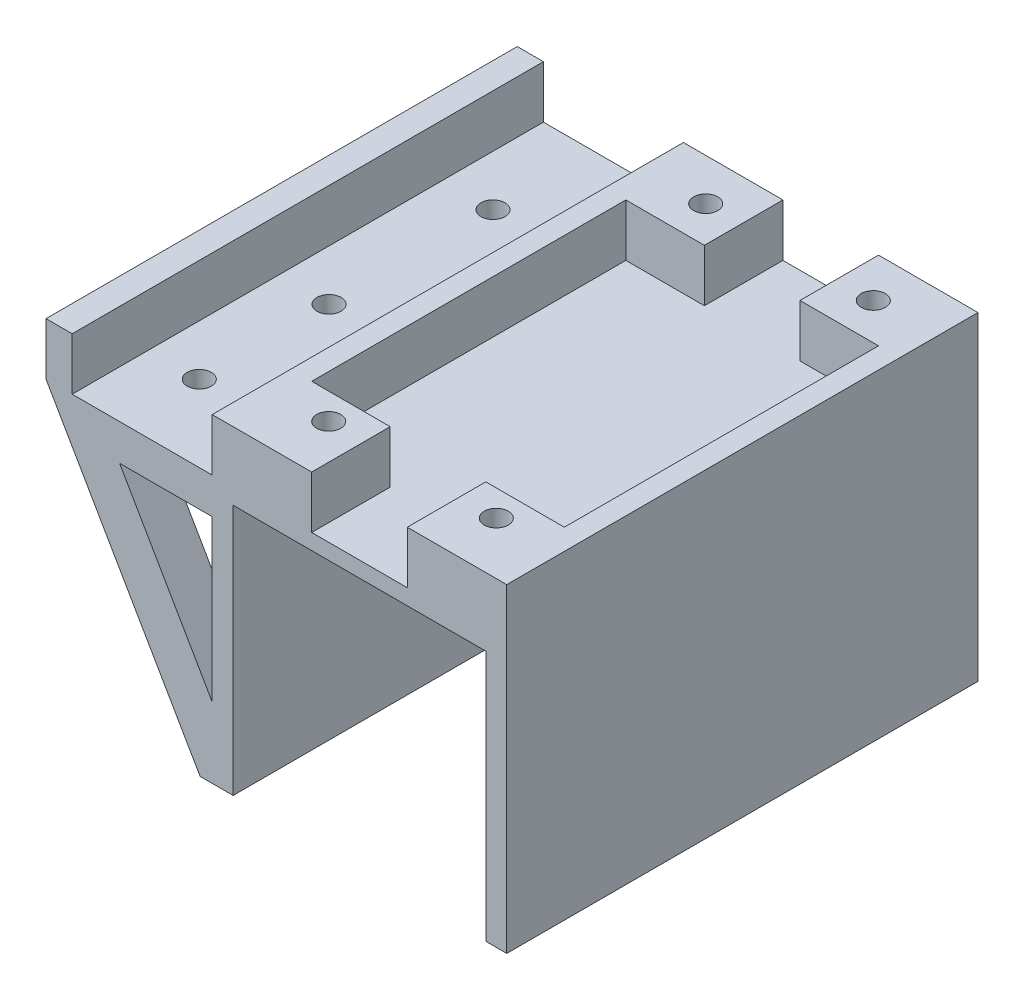
SolidWorks part; units mm, degrees
ref_plane "Front" through (0, 0, 0) normal (0, 0, 1) x (1, 0, 0)
ref_plane "Top" through (0, 0, 0) normal (0, 1, 0) x (1, 0, 0)
ref_plane "Right" through (0, 0, 0) normal (1, 0, 0) x (0, 0, -1)
sketch "Sketch1" plane through (0, 0, 0) normal (0, 0, 1) x (1, 0, 0)
  line L0 (0, 0) -> (0, 70)
  line L1 (0, 70) -> (56.254, 70)
  line L2 (56.254, 70) -> (56.254, 0)
  line L3 (56.254, 0) -> (52.254, 0)
  line L4 (52.254, 0) -> (52.254, 65)
  line L5 (52.254, 65) -> (4, 65)
  line L6 (4, 65) -> (4, 0)
  line L7 (4, 0) -> (0, 0)
  line L9 (4, 55) -> (52.254, 55)
  line L10 (4, 55) -> (4, 52)
  line L11 (4, 52) -> (52.254, 52)
  line L12 (52.254, 55) -> (52.254, 52)
  dimension "D1" = 48.254
  dimension "D2" = 4
  dimension "D3" = 4
  dimension "D4" = 5
  dimension "D5" = 70
  dimension "D6" = 3
  dimension "D7" = 10
extrude "Boss-Extrude1" add sketch "Sketch1" along normal blind 70 contours L7 L6 L5 L4 L3 L2 L1 L0 | L9 L12 L11 L10 region at (0.898, 35, 0)
sketch "Sketch3" plane through (0, 0, 70) normal (0, 0, 1) x (1, 0, 0)
  line L0 (0, 70) -> (-40.3946, 70)
  line L1 (-40.3946, 70) -> (0, 0.0344)
  line L2 (0, 0) -> (0, 70) construction
  line L3 (0, 0.0344) -> (0, 70)
  line L4 (0, 70) -> (0, 62.5)
  line L5 (0, 62.5) -> (-26, 62.5)
  line L6 (-26, 62.5) -> (0, 17.4667)
  line L7 (0, 17.4667) -> (0, 0.0344)
  line M11 (0, 70) -> (0, 0)
  dimension "D1" = 60
  dimension "D2" = 180
  dimension "D3" = 7.5
  dimension "D4" = 26
extrude "Boss-Extrude3" add sketch "Sketch3" against normal blind 8 contours L6 L5 L0 L1 M11 region at (-16.8587, 46.1047, 70)
sketch "Sketch4" plane through (0, 0, 0) normal (0, 0, -1) x (-1, 0, 0)
  line L0 (0, 70) -> (40.3946, 70)
  line L1 (40.3946, 70) -> (0, 0)
  line L2 (0, 0) -> (0, 17.4667)
  line L3 (0, 17.4667) -> (26, 62.5)
  line L4 (26, 62.5) -> (0, 62.5)
  line L5 (0, 62.5) -> (0, 70)
extrude "Boss-Extrude4" add sketch "Sketch4" against normal blind 8
ref_plane "Plane1" through (0, 0, 39) normal (0, 0, -1) x (-1, 0, 0)
sketch "Sketch5" plane through (0, 0, 39) normal (0, 0, -1) x (-1, 0, 0)
  line L0 (0, 62.5) -> (0, 70)
  line L1 (0, 70) -> (40.3946, 70)
  line L2 (40.3946, 70) -> (0, 0)
  line L3 (0, 0) -> (0, 17.4667)
  line L4 (0, 17.4667) -> (26, 62.5)
  line L5 (26, 62.5) -> (0, 62.5)
extrude "Boss-Extrude5" add sketch "Sketch5" along normal blind 8
sketch "Sketch6" plane through (0, 0, 0) normal (0, 0, -1) x (-1, 0, 0)
  line L5 (0, 62.5) -> (36.0666, 62.5)
  line L6 (0, 0) -> (40.3946, 70) construction
  line L7 (36.0666, 62.5) -> (40.3946, 70)
  line L8 (40.3946, 70) -> (0, 70)
  line L9 (40.3946, 70) -> (-56.254, 70) construction
  line L10 (0, 70) -> (0, 62.5)
  line L11 (-4, 0) -> (0, 0)
  line L12 (0, 0) -> (7.5019, 13)
  line L13 (7.5019, 13) -> (-4, 13)
  line L14 (-4, 52) -> (-4, 0) construction
  line L15 (-4, 13) -> (-4, 0)
  dimension "D1" = 13
extrude "Boss-Extrude6" add sketch "Sketch6" against normal blind 70
sketch "Sketch7" plane through (0, 0, 70) normal (0, 0, 1) x (1, 0, 0)
  line L0 (0, 17.4667) -> (0, 62.5) construction
  line L1 (-40.3946, 70) -> (0, 70)
  line L2 (-40.3946, 70) -> (-40.3946, 53)
  line L3 (-40.3946, 53) -> (0, 53)
  line L4 (0, 70) -> (0, 53)
  dimension "D1" = 17
extrude "Cut-Extrude3" cut sketch "Sketch7" against normal blind 70
sketch "Sketch8" plane through (0, 0, 0) normal (0, 0, -1) x (-1, 0, 0)
  line L1 (-4, 55) -> (-4, 52)
  line L2 (-4, 52) -> (-52.254, 52) construction
  line L3 (-4, 52) -> (30.0074, 52)
  line L4 (0, 0) -> (30.5845, 53) construction
  line L6 (30.0074, 52) -> (31.7386, 55)
  line L7 (31.7386, 55) -> (-4, 55)
  dimension "D1" = 180
extrude "Boss-Extrude7" add sketch "Sketch8" against normal blind 70
sketch "Sketch11" plane through (0, 0, 70) normal (0, 0, 1) x (1, 0, 0)
  line L0 (-31.7386, 55) -> (0, 0)
  line L3 (-31.7386, 55) -> (0, 55) construction
  line L4 (-27.289, 55) -> (-31.7386, 55)
  line L5 (-27.289, 55) -> (-3.0537, 13)
  line L6 (-3.0537, 13) -> (0, 0)
extrude "Boss-Extrude10" add sketch "Sketch11" against normal blind 8
sketch "Sketch12" plane through (0, 0, 70) normal (0, 0, 1) x (1, 0, 0)
  line L0 (-31.7386, 55) -> (-27.7598, 48.1051)
  line L1 (0, 0) -> (-31.7386, 55) construction
  line L2 (-27.7598, 48.1051) -> (0, 48.1051)
  line L3 (0, 17.4667) -> (0, 52) construction
  line L4 (0, 48.1051) -> (0, 55)
  line L5 (0, 55) -> (-31.7386, 55)
extrude "Boss-Extrude11" add sketch "Sketch12" against normal blind 70
sketch "Sketch13" plane through (0, 0, 0) normal (0, -1, 0) x (1, 0, 0)
  line L1 (67.4394, -10.6205) -> (-15.562, -10.6205)
  line L2 (67.4394, -10.6205) -> (67.4394, 77.2481)
  line L3 (67.4394, 77.2481) -> (-15.562, 77.2481)
  line L4 (-15.562, -10.6205) -> (-15.562, 77.2481)
extrude "Cut-Extrude4" cut sketch "Sketch13" against normal blind 4
sketch "Sketch14" plane through (0, 0, 70) normal (0, 0, 1) x (1, 0, 0)
  line L0 (-2.3083, 4) -> (-31.7386, 55)
  line L1 (-31.7386, 55) -> (0, 55)
  line L2 (0, 55) -> (0, 70)
  line L3 (0, 70) -> (56.254, 70)
  line L4 (56.254, 70) -> (56.254, 4)
  line L5 (56.254, 4) -> (52.254, 4)
  line L6 (52.254, 4) -> (52.254, 52)
  line L7 (52.254, 52) -> (4, 52)
  line L8 (4, 52) -> (4, 4)
  line L9 (4, 4) -> (-2.3083, 4)
  line L14 (-17.6891, 48.1051) -> (0, 48.1051)
  line L15 (52.254, 55) -> (4, 55)
  line L16 (52.254, 55) -> (52.254, 65)
  line L17 (52.254, 65) -> (4, 65)
  line L18 (4, 55) -> (4, 65)
  line L19 (-17.6891, 48.1051) -> (0, 48.1051) construction
  line L20 (0, 48.1051) -> (0, 17.4667)
  line L21 (0, 17.4667) -> (-17.6891, 48.1051)
extrude "Boss-Extrude12" add sketch "Sketch14" along normal blind 20
sketch "Sketch15" plane through (0, 0, 90) normal (0, 0, 1) x (1, 0, 0)
  line L0 (56.254, 4) -> (56.254, 70) construction
  line L1 (56.254, 65) -> (37.264, 65)
  line L2 (56.254, 65) -> (56.254, 55)
  line L3 (56.254, 55) -> (37.264, 55)
  line L4 (37.264, 65) -> (37.264, 55)
  line L5 (4, 55) -> (52.254, 55) construction
  dimension "D1" = 18.99
sketch "Sketch16" plane through (0, 0, 90) normal (0, 0, 1) x (1, 0, 0)
  line L1 (0, 70) -> (56.254, 70)
  line L2 (0, 70) -> (0, 65)
  line L3 (0, 65) -> (56.254, 65)
  line L4 (56.254, 70) -> (56.254, 65)
extrude "Cut-Extrude5" cut sketch "Sketch16" against normal blind 100
sketch "Sketch17" plane through (0, 65, 0) normal (0, 1, 0) x (1, 0, 0)
  line L1 (52.254, 0) -> (37.254, 0)
  line L2 (52.254, 0) -> (52.254, -15)
  line L3 (52.254, -15) -> (37.254, -15)
  line L4 (37.254, 0) -> (37.254, -15)
  line L5 (52.254, -90) -> (37.254, -90)
  line L6 (52.254, -90) -> (52.254, -75)
  line L7 (52.254, -75) -> (37.254, -75)
  line L8 (37.254, -90) -> (37.254, -75)
  dimension "D1" = 15
  dimension "D2" = 15
  dimension "D3" = 15
  dimension "D4" = 15
extrude "Boss-Extrude14" add sketch "Sketch17" against normal blind 13
sketch "Sketch21" plane through (0, 52, 0) normal (0, -1, 0) x (-1, 0, 0)
  circle A0 centre (-44.254, -80) radius 2.3
  circle A1 centre (-44.254, -8) radius 2.3
sketch "Sketch22" plane through (0, 52, 0) normal (0, -1, 0) x (1, 0, 0)
  line L1 (48.0965, 6.0036) -> (47.9041, 10.3295)
  line L2 (47.9041, 10.3295) -> (44.0617, 12.3259)
  line L3 (44.0617, 12.3259) -> (40.4115, 9.9964)
  line L4 (40.4115, 9.9964) -> (40.6039, 5.6705)
  line L5 (40.6039, 5.6705) -> (44.4463, 3.6741)
  line L6 (44.4463, 3.6741) -> (48.0965, 6.0036)
  line L7 (45.2007, 75.7746) -> (48.3866, 78.7072)
  line L8 (48.3866, 78.7072) -> (47.4399, 82.9325)
  line L9 (47.4399, 82.9325) -> (43.3073, 84.2254)
  line L10 (43.3073, 84.2254) -> (40.1214, 81.2928)
  line L11 (40.1214, 81.2928) -> (41.0681, 77.0675)
  line L12 (41.0681, 77.0675) -> (45.2007, 75.7746)
  circle A0 centre (44.254, 8) radius 3.75 construction
  circle A1 centre (44.254, 80) radius 3.75 construction
  point P10 (42.2366, 11.1611)
  dimension "D1" = 7.5
  dimension "D2" = 7.5
extrude "Cut-Extrude8" cut sketch "Sketch22" against normal blind 5
extrude "Cut-Extrude9" cut sketch "Sketch21" against normal blind 15
sketch "Sketch23" plane through (0, 0, 0) normal (-0.8661, -0.4998, 0) x (0, 0, 1)
  line L0 (90, 63.5007) -> (90, 4.6182) construction
  line L1 (70, 55.5401) -> (82, 55.5401)
  line L2 (70, 55.5401) -> (70, 15.0093)
  line L3 (70, 15.0093) -> (82, 15.0093)
  line L4 (82, 55.5401) -> (82, 15.0093)
  line L5 (62, 55.5401) -> (62, 15.0093) construction
  dimension "D1" = 8
  dimension "D2" = 8
extrude "Cut-Extrude10" cut sketch "Sketch23" against normal blind 9
sketch "Sketch25" plane through (0, 48.1051, 0) normal (0, -1, 0) x (-1, 0, 0)
  circle A0 centre (17.0755, -19.3006) radius 2.3
  circle A1 centre (17.0755, -50.6137) radius 2.3
extrude "Cut-Extrude11" cut sketch "Sketch25" against normal blind 20
sketch "Sketch26" plane through (0, 48.1051, 0) normal (0, -1, 0) x (1, 0, 0)
  circle A0 centre (-17.0755, 75.3913) radius 2.3
extrude "Cut-Extrude12" cut sketch "Sketch26" against normal blind 20
sketch "Sketch27" plane through (0, 0, 90) normal (0, 0, 1) x (1, 0, 0)
  line L0 (-23.3104, 48.1051) -> (-27.7598, 48.1051)
  line L1 (-31.7386, 55) -> (-2.3083, 4) construction
  line L2 (-27.7598, 48.1051) -> (-31.7386, 55)
  line L3 (-31.7386, 55) -> (-23.3104, 55)
  line L4 (0, 55) -> (-31.7386, 55) construction
  line L5 (-23.3104, 55) -> (-23.3104, 48.1051)
extrude "Boss-Extrude16" add sketch "Sketch27" against normal blind 20
sketch "Sketch28" plane through (0, 55, 0) normal (0, 1, 0) x (1, 0, 0)
  line L0 (4, -90) -> (37.254, -90) construction
  line L1 (4, 0) -> (19, 0)
  line L2 (4, 0) -> (4, -15)
  line L3 (4, -15) -> (19, -15)
  line L4 (19, 0) -> (19, -15)
  line L5 (4, -90) -> (19, -90)
  line L6 (4, -90) -> (4, -75)
  line L7 (4, -75) -> (19, -75)
  line L8 (19, -90) -> (19, -75)
  line L9 (4, 0) -> (4, -90) construction
  dimension "D1" = 15
  dimension "D2" = 15
  dimension "D3" = 15
  dimension "D4" = 15
extrude "Boss-Extrude17" add sketch "Sketch28" along normal blind 10
sketch "Sketch29" plane through (0, 52, 0) normal (0, -1, 0) x (-1, 0, 0)
  circle A0 centre (-12.254, -8) radius 2.3
  circle A1 centre (-12.254, -80) radius 2.3
extrude "Cut-Extrude13" cut sketch "Sketch29" against normal blind 20
sketch "Sketch30" plane through (0, 48.1051, 0) normal (0, -1, 0) x (1, 0, 0)
  line L1 (-27.7598, 70) -> (-17.3688, 70)
  line L2 (-27.7598, 70) -> (-27.7598, 82)
  line L3 (-27.7598, 82) -> (-17.3688, 82)
  line L4 (-17.3688, 70) -> (-17.3688, 82)
extrude "Boss-Extrude18" add sketch "Sketch30" against normal blind 5
sketch "Sketch31" plane through (0, 48.1051, 0) normal (0, -1, 0) x (1, 0, 0)
  circle A0 centre (-17.0755, 75.3913) radius 2.3
extrude "Cut-Extrude14" cut sketch "Sketch31" against normal blind 45
sketch "Sketch36" plane through (0, 55, 0) normal (0, 1, 0) x (1, 0, 0)
  line L0 (0, -90) -> (-31.7386, -90) construction
  line L1 (-31.7386, 0) -> (-31.1386, 0)
  line L2 (-31.7386, 0) -> (-31.7386, -90)
  line L3 (-31.7386, -90) -> (-31.1386, -90)
  line L4 (-31.1386, 0) -> (-31.1386, -90)
  line L5 (-27.5386, 0) -> (-27.5386, -90)
  line L6 (-27.5386, 0) -> (-26.9386, 0)
  line L7 (-26.9386, 0) -> (-26.9386, -90)
  line L8 (-27.5386, -90) -> (-26.9386, -90)
  line L9 (-23.3386, 0) -> (-23.3386, -90)
  line L10 (-23.3386, 0) -> (-22.7386, 0)
  line L11 (-22.7386, 0) -> (-22.7386, -90)
  line L12 (-23.3386, -90) -> (-22.7386, -90)
  line L13 (-19.1386, 0) -> (-19.1386, -90)
  line L14 (-19.1386, 0) -> (-18.5386, 0)
  line L15 (-18.5386, 0) -> (-18.5386, -90)
  line L16 (-19.1386, -90) -> (-18.5386, -90)
  line L17 (-14.9386, 0) -> (-14.9386, -90)
  line L18 (-14.9386, 0) -> (-14.3386, 0)
  line L19 (-14.3386, 0) -> (-14.3386, -90)
  line L20 (-14.9386, -90) -> (-14.3386, -90)
  line L21 (-10.7386, 0) -> (-10.7386, -90)
  line L22 (-10.7386, 0) -> (-10.1386, 0)
  line L23 (-10.1386, 0) -> (-10.1386, -90)
  line L24 (-10.7386, -90) -> (-10.1386, -90)
  line L25 (-6.5386, 0) -> (-6.5386, -90)
  line L26 (-6.5386, 0) -> (-5.9386, 0)
  line L27 (-5.9386, 0) -> (-5.9386, -90)
  line L28 (-6.5386, -90) -> (-5.9386, -90)
  line L29 (-2.3386, 0) -> (-2.3386, -90)
  line L30 (-2.3386, 0) -> (-1.7386, 0)
  line L31 (-1.7386, 0) -> (-1.7386, -90)
  line L32 (-2.3386, -90) -> (-1.7386, -90)
  line L33 (-31.7386, 0) -> (-27.5386, 0) construction
  dimension "D1" = 0.6
  dimension "D3" = 4.2
  dimension "D2" = 8
sketch "Sketch37" plane through (0, 55, 0) normal (0, 1, 0) x (1, 0, 0)
  line L0 (19, 0) -> (37.254, 0) construction
  line L13 (4, -6) -> (4, -6.5)
  line L14 (4, -15) -> (4, -75) construction
  line L15 (4, -2) -> (53, -2)
  line L16 (4, -2) -> (4, -2.5)
  line L17 (4, -2.5) -> (53, -2.5)
  line L18 (53, -2) -> (53, -2.5)
  line L19 (4, -6) -> (53, -6)
  line L20 (53, -6) -> (53, -6.5)
  line L21 (4, -6.5) -> (53, -6.5)
  line L22 (4, -10) -> (4, -10.5)
  line L23 (4, -10) -> (53, -10)
  line L24 (53, -10) -> (53, -10.5)
  line L25 (4, -10.5) -> (53, -10.5)
  line L26 (4, -14) -> (4, -14.5)
  line L27 (4, -14) -> (53, -14)
  line L28 (53, -14) -> (53, -14.5)
  line L29 (4, -14.5) -> (53, -14.5)
  line L30 (4, -18) -> (4, -18.5)
  line L31 (4, -18) -> (53, -18)
  line L32 (53, -18) -> (53, -18.5)
  line L33 (4, -18.5) -> (53, -18.5)
  line L34 (4, -22) -> (4, -22.5)
  line L35 (4, -22) -> (53, -22)
  line L36 (53, -22) -> (53, -22.5)
  line L37 (4, -22.5) -> (53, -22.5)
  line L38 (4, -26) -> (4, -26.5)
  line L39 (4, -26) -> (53, -26)
  line L40 (53, -26) -> (53, -26.5)
  line L41 (4, -26.5) -> (53, -26.5)
  line L42 (4, -30) -> (4, -30.5)
  line L43 (4, -30) -> (53, -30)
  line L44 (53, -30) -> (53, -30.5)
  line L45 (4, -30.5) -> (53, -30.5)
  line L46 (4, -34) -> (4, -34.5)
  line L47 (4, -34) -> (53, -34)
  line L48 (53, -34) -> (53, -34.5)
  line L49 (4, -34.5) -> (53, -34.5)
  line L50 (4, -38) -> (4, -38.5)
  line L51 (4, -38) -> (53, -38)
  line L52 (53, -38) -> (53, -38.5)
  line L53 (4, -38.5) -> (53, -38.5)
  line L54 (4, -42) -> (4, -42.5)
  line L55 (4, -42) -> (53, -42)
  line L56 (53, -42) -> (53, -42.5)
  line L57 (4, -42.5) -> (53, -42.5)
  line L58 (4, -46) -> (4, -46.5)
  line L59 (4, -46) -> (53, -46)
  line L60 (53, -46) -> (53, -46.5)
  line L61 (4, -46.5) -> (53, -46.5)
  line L62 (4, -50) -> (4, -50.5)
  line L63 (4, -50) -> (53, -50)
  line L64 (53, -50) -> (53, -50.5)
  line L65 (4, -50.5) -> (53, -50.5)
  line L66 (4, -54) -> (4, -54.5)
  line L67 (4, -54) -> (53, -54)
  line L68 (53, -54) -> (53, -54.5)
  line L69 (4, -54.5) -> (53, -54.5)
  line L70 (4, -58) -> (4, -58.5)
  line L71 (4, -58) -> (53, -58)
  line L72 (53, -58) -> (53, -58.5)
  line L73 (4, -58.5) -> (53, -58.5)
  line L74 (4, -62) -> (4, -62.5)
  line L75 (4, -62) -> (53, -62)
  line L76 (53, -62) -> (53, -62.5)
  line L77 (4, -62.5) -> (53, -62.5)
  line L78 (4, -66) -> (4, -66.5)
  line L79 (4, -66) -> (53, -66)
  line L80 (53, -66) -> (53, -66.5)
  line L81 (4, -66.5) -> (53, -66.5)
  line L82 (4, -70) -> (4, -70.5)
  line L83 (4, -70) -> (53, -70)
  line L84 (53, -70) -> (53, -70.5)
  line L85 (4, -70.5) -> (53, -70.5)
  line L86 (4, -74) -> (4, -74.5)
  line L87 (4, -74) -> (53, -74)
  line L88 (53, -74) -> (53, -74.5)
  line L89 (4, -74.5) -> (53, -74.5)
  line L90 (4, -78) -> (4, -78.5)
  line L91 (4, -78) -> (53, -78)
  line L92 (53, -78) -> (53, -78.5)
  line L93 (4, -78.5) -> (53, -78.5)
  line L94 (4, -82) -> (4, -82.5)
  line L95 (4, -82) -> (53, -82)
  line L96 (53, -82) -> (53, -82.5)
  line L97 (4, -82.5) -> (53, -82.5)
  line L98 (4, -86) -> (4, -86.5)
  line L99 (4, -86) -> (53, -86)
  line L100 (53, -86) -> (53, -86.5)
  line L101 (4, -86.5) -> (53, -86.5)
  dimension "D1" = 49
  dimension "D2" = 0.5
  dimension "D3" = 2
  dimension "D4" = 22
sketch "Sketch40" plane through (0, 65, 0) normal (0, 1, 0) x (1, 0, 0)
  circle A0 centre (-17.0755, -19.3006) radius 2.2732
  circle A1 centre (-17.0755, -50.6137) radius 2.3827
  circle A2 centre (-17.0755, -75.3913) radius 2.3828
  circle A3 centre (12.254, -80) radius 2.5607
  circle A4 centre (44.254, -80) radius 2.2791
  circle A5 centre (44.254, -8) radius 2.3112
  circle A6 centre (12.254, -8) radius 2.3
sketch "Sketch41" plane through (0, 55, 0) normal (0, 1, 0) x (1, 0, 0)
  line L0 (-31.7386, 0) -> (0, 0) construction
  line L1 (-31.7386, -90) -> (-26.7386, -90)
  line L2 (-31.7386, -90) -> (-31.7386, 0)
  line L3 (-31.7386, 0) -> (-26.7386, 0)
  line L4 (-26.7386, -90) -> (-26.7386, 0)
  dimension "D1" = 5
extrude "Boss-Extrude19" add sketch "Sketch41" along normal blind 10
